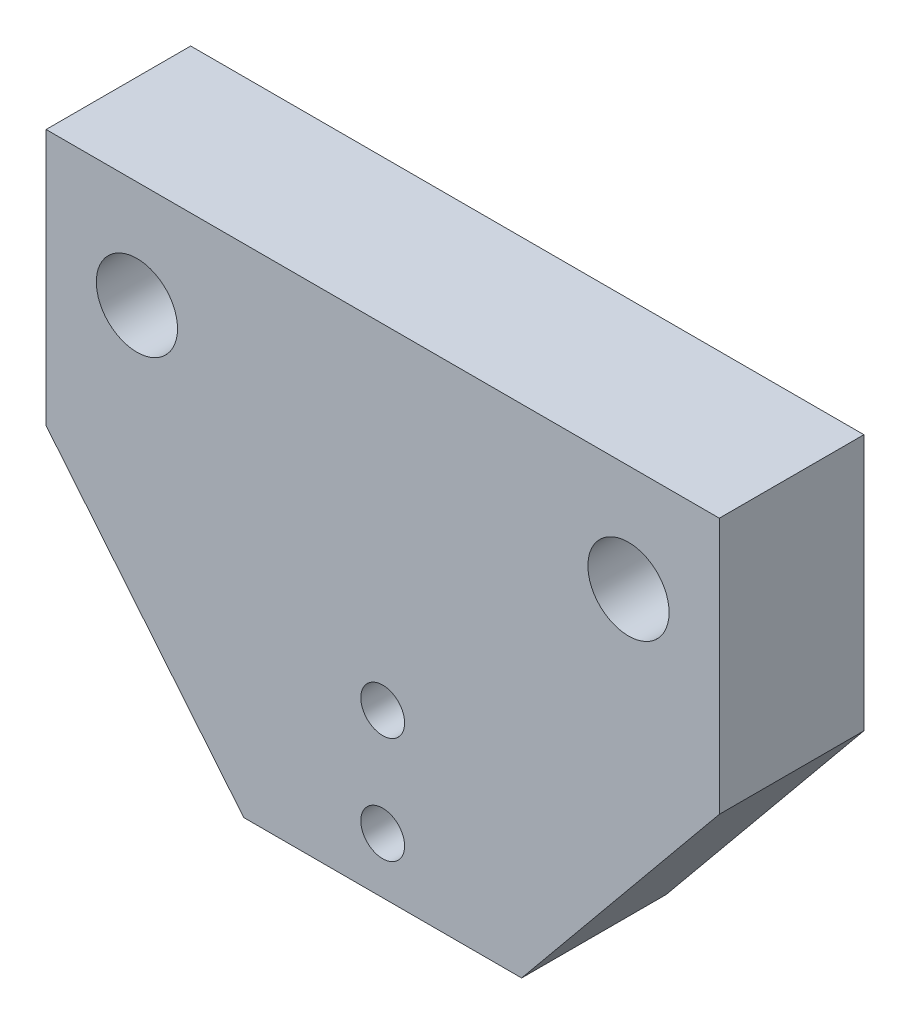
SolidWorks part; units mm, degrees
ref_plane "Front Plane" through (0, 0, 0) normal (0, 0, 1) x (1, 0, 0)
ref_plane "Top Plane" through (0, 0, 0) normal (0, 1, 0) x (1, 0, 0)
ref_plane "Right Plane" through (0, 0, 0) normal (1, 0, 0) x (0, 0, -1)
sketch "Sketch1" plane through (0, 0, 0) normal (0, 0, 1) x (1, 0, 0)
  line L0 (0, 0) -> (0, 60.5723) construction
  line L1 (0, -55) -> (0, 55) construction
  line L2 (55, 0) -> (-55, 0) construction
  line L3 (31.5, 10) -> (-31.5, 10)
  line L4 (-31.5, 10) -> (-31.5, -14)
  line L5 (-31.5, -14) -> (31.5, -14)
  line L6 (31.5, 10) -> (31.5, -14)
  line L7 (0, -36.5157) -> (-13, -36.5157)
  line L8 (0, -36.5157) -> (13, -36.5157)
  line L9 (-13, -36.5157) -> (-31.5, -14)
  line L10 (13, -36.5157) -> (31.5, -14)
  circle A0 centre (-23, 0) radius 3.3
  circle A1 centre (-23, 0) radius 3.8
  circle A2 centre (23, 0) radius 3.3
  circle A3 centre (23, 0) radius 3.8
  circle A4 centre (0, -21.3221) radius 2.05
  circle A5 centre (0, -31.3) radius 2.05
  point P5 (-23, 0)
  point P6 (23, 0)
  point P12 (0, -36.5157)
  point P17 (0, -14)
  point P21 (0, 10)
  dimension "D3" = 10
  dimension "D7" = 6.6
  dimension "D8" = 7.6
  dimension "D9" = 4.1
  dimension "D10" = 4.1
  dimension "D1" = 23
  dimension "D2" = 23
  dimension "D4" = 63
  dimension "D5" = 24
  dimension "D6" = 13
extrude "Boss-Extrude1" add sketch "Sketch1" along normal blind 13.53 contours L6 L3 L4 L5 A1 A3 region at (0, -2.1277, 0)
extrude "Boss-Extrude2" add sketch "Sketch1<3>" along normal blind 13.53 contours L8 L10 L5 L9 L7 A5 A4 region at (0, -23.627, 0)
sketch "Sketch1<3>" plane through (0, 0, 0) normal (0, 0, 1) x (1, 0, 0) same geometry as "Sketch1"
